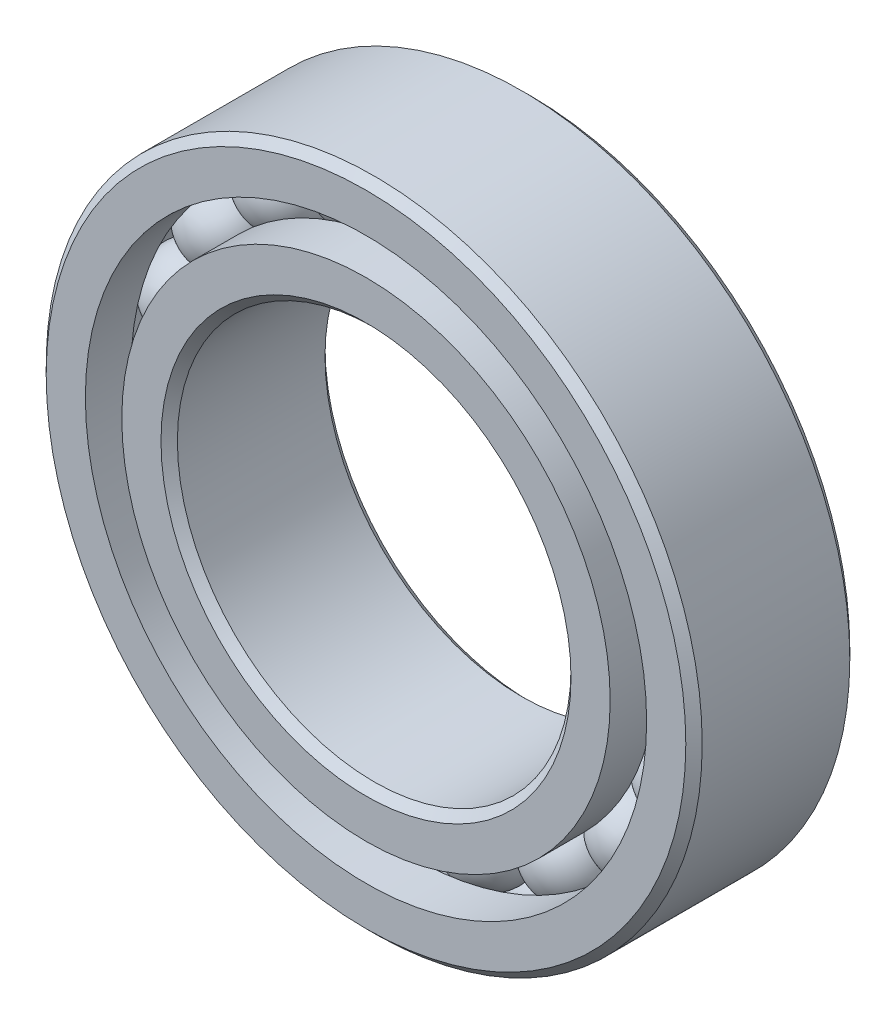
SolidWorks part; units mm, degrees
material "AISI 304"
ref_plane "Front Plane" through (0, 0, 0) normal (0, 0, 1) x (1, 0, 0)
ref_plane "Top Plane" through (0, 0, 0) normal (0, 1, 0) x (1, 0, 0)
ref_plane "Right Plane" through (0, 0, 0) normal (1, 0, 0) x (0, 0, -1)
sketch "Sketch1" plane through (0, 0, 0) normal (1, 0, 0) x (0, 0, -1)
  line L0 (-1.25, 0) -> (1.25, 0) construction
  line L1 (0, 5) -> (0, -5) construction
  line L2 (1.125, 5) -> (-1.125, 5)
  line L3 (-1.125, 5) -> (-1.25, 4.875)
  line L4 (-1.25, 4.875) -> (-1.25, 4.2778)
  line L5 (-1.25, 4.2778) -> (-0.5556, 4.2778)
  line L6 (1.25, 4.2778) -> (0.5556, 4.2778)
  line L7 (1.25, 4.875) -> (1.25, 4.2778)
  line L8 (1.125, 5) -> (1.25, 4.875)
  line L9 (0, 5) -> (0, 4) construction
  line L10 (0, 4) -> (0, 3) construction
  arc A0 (-0.5556, 4.2778) -> (0.5556, 4.2778) centre (0, 4) cw
  arc A1 (-0.5556, 4.2778) -> (0.5556, 4.2778) centre (0, 4) ccw construction
  point P14 (0, 3)
  point P15 (0, -3)
  dimension "Width" = 2.5
  dimension "OD" = 10
  dimension "D1" = 45
  dimension "D2" = 0.125
  dimension "D3" = 1.1111
  dimension "Shaft Dia" = 6
  dimension "D4" = 0.2778
revolve "Revolve1" add sketch "Sketch1" angle 360 about L0
sketch "Sketch2" plane through (0, 0, 0) normal (1, 0, 0) x (0, 0, -1)
  line L0 (-1.25, 3.7222) -> (-0.5556, 3.7222)
  line L1 (-1.25, 4.875) -> (-1.25, -4.875) construction
  line L2 (-1.25, 3.7222) -> (-1.25, 3.125)
  line L3 (-1.25, 3.125) -> (-1.125, 3)
  line L4 (-1.125, 3) -> (1.125, 3)
  line L5 (0, 5) -> (0, -5) construction
  line L6 (0, 3) -> (0, 3.3789) construction
  line L7 (0, 3.3789) -> (0, 3) construction
  line L8 (-1.25, 3.7222) -> (-1.25, 2.5278) construction
  line L10 (1.25, 3.7222) -> (0.5556, 3.7222)
  line L11 (1.25, 3.7222) -> (1.25, 3.125)
  line L12 (1.25, 3.125) -> (1.125, 3)
  arc A0 (-0.5556, 3.7222) -> (0.5556, 3.7222) centre (0, 4) ccw
  arc A1 (0.5556, 4.2778) -> (-0.5556, 4.2778) centre (0, 4) ccw construction
  circle A2 centre (0, 4) radius 0.6211 construction
  dimension "D1" = 0.125
  dimension "D2" = 45
revolve "Revolve2" add sketch "Sketch2" angle 360 about L0
sketch "Sketch3" plane through (0, 0, 0) normal (1, 0, 0) x (0, 0, -1)
  line L0 (-0.6211, 4) -> (0.6211, 4)
  line L1 (0, 4) -> (0, 0) construction
  circle A1 centre (0, 4) radius 0.6211 construction
  arc A2 (-0.6211, 4) -> (0.6211, 4) centre (0, 4) cw
  arc A3 (0.5556, 4.2778) -> (-0.5556, 4.2778) centre (0, 4) ccw construction
  dimension "D1" = 1.2423
revolve "Revolve3" add sketch "Sketch3" angle 360 about L0
ref_axis "Axis1" through (0, 0, -1.25) along (0, 0, 1)
pattern_circular "CirPattern1" count 19 every 18.947 about axis through (0, 0, -1.25) along (0, 0, 1) of bodies 104
sketch "Sketch6" plane through (0, 0, 0) normal (0, 1, 0) x (1, 0, 0)
  point P0 (5, -1.25)
  point P1 (5, 1.25)
  dimension "D1" = 2.5
ref_axis "Center Axis 1" through (0, 0, -2.6235) along (0, 0, 1)
ref_plane "Contact Plane 1" through (0, 0, 1.25) normal (0, 0, 1) x (1, 0, 0)
ref_plane "Contact Plane 2" through (0, 0, -1.25) normal (0, 0, -1) x (-1, 0, 0)
equation "\"D2@Sketch1\" = \"Width@Sketch1\"*.05"
equation "\"D3@Sketch1\" = \"Width@Sketch1\"/2.25"
equation "\"D4@Sketch1\" = \"D3@Sketch1\"/4"
equation "\"Balls@CirPattern1\"=\"D2@Sketch3\"*2*pi/\"D1@Sketch3\"-1"
equation "\"D2@CirPattern1\" = 360/\"Balls@CirPattern1\""
equation "\"D1@Sketch2\"=\"D2@Sketch1\""
equation "\"D1@Sketch6\"=\"Width@Sketch1\""
